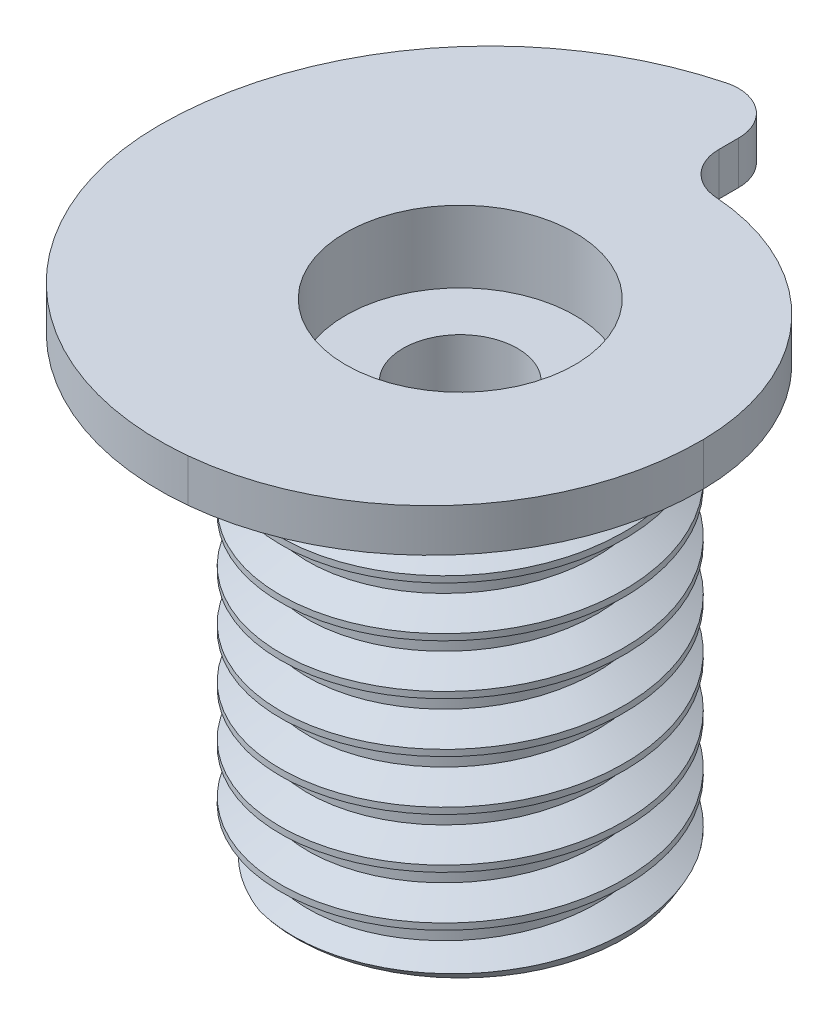
SolidWorks part; units mm, degrees
ref_plane "Front Plane" through (0, 0, 0) normal (0, 0, 1) x (1, 0, 0)
ref_plane "Top Plane" through (0, 0, 0) normal (0, 1, 0) x (1, 0, 0)
ref_plane "Right Plane" through (0, 0, 0) normal (1, 0, 0) x (0, 0, -1)
sketch "Sketch1" plane through (0, 0, 0) normal (1, 0, 0) x (0, 0, -1)
  line L4 (12, 30) -> (12, 0)
  line L6 (0, 0) -> (0, 30) construction
  line L7 (12, 30) -> (4, 30)
  line L10 (4, 30) -> (4, 5)
  line L11 (4, 5) -> (8, 5)
  line L12 (8, 5) -> (8, 0)
  line L13 (8, 0) -> (12, 0)
  dimension "D1" = 8
  dimension "D2" = 8
  dimension "D3" = 5
  dimension "D6" = 30
  dimension "D7" = 12
revolve "Revolve1" add sketch "Sketch1" angle 360 about L6
chamfer "Chamfer1" distance 1 angle 30 1 edges at (0, 0, -12) first distance on face at (0, 30, -12)
thread "Thread1" pitch 3.5 method cut profile "Thread Profile1" start angle 0, offset 0, length 48, pitch 3.5, diameter 24
ref_plane "Plane1" through (-12, 30, 0) normal (0, 0, 1) x (-1, 0, 0)
sketch "Thread Profile1" plane through (-12, 30, 0) normal (0, 0, 1) x (-1, 0, 0)
  line L0 (0, 0) -> (0, 3.5) construction
  line L11 (0, 0) -> (0, 3.0625)
  line L12 (0, 3.0625) -> (-1.8944, 1.9687)
  line L13 (-1.8944, 1.9687) -> (-1.8944, 1.0937)
  line L15 (-1.8944, 1.0937) -> (0, 0)
  line L17 (-1.8944, 1.5312) -> (0, 1.5312) construction
  point P2 (0, 0)
  dimension "Pitch" = 3.5
  dimension "Profile_Angle" = 60
  dimension "Profile_Land" = 0.875
  dimension "Profile_Height" = 1.8944
sketch "Sketch2" plane through (0, 30, 0) normal (0, 1, 0) x (1, 0, 0)
  line L1 (0, 11.547) -> (-10, -5.7735) construction
  line L2 (-10, -5.7735) -> (10, -5.7735) construction
  line L3 (10, -5.7735) -> (0, 11.547) construction
  circle A0 centre (0, 0) radius 5.7735 construction
  circle A1 centre (0, 11.547) radius 1.5
  circle A2 centre (10, -5.7735) radius 1.5
  circle A3 centre (-10, -5.7735) radius 1.5
  dimension "D2" = 3
  dimension "D1" = 20
extrude "Cut-Extrude1" [suppressed] cut sketch "Sketch2" against normal blind 4
sketch "Sketch3" plane through (0, 30, 0) normal (0, 1, 0) x (1, 0, 0)
  line L0 (0, 23) -> (0, -23) construction
  line L1 (-23, 0) -> (23, 0) construction
  line L2 (0, 23) -> (0, 15)
  circle A1 centre (0, 0) radius 15 construction
  circle A2 centre (0, 0) radius 17 construction
  circle A3 centre (0, 0) radius 19 construction
  circle A4 centre (0, 0) radius 21 construction
  circle A5 centre (0, 0) radius 23 construction
  arc A6 (0, 23) -> (-21, 0) centre (2.0952, 0) ccw
  arc A7 (-21, 0) -> (0, -19) centre (-1.9048, 0) ccw
  arc A8 (0, -19) -> (17, 0) centre (-1.8838, -0.2092) ccw
  arc A9 (17, 0) -> (0, 15) centre (1.7331, -0.1692) ccw
  dimension "D1" = 30
  dimension "D2" = 2
  dimension "D3" = 2
  dimension "D4" = 2
  dimension "D5" = 2
extrude "Boss-Extrude1" add sketch "Sketch3" along normal blind 3
sketch "Sketch4" plane through (0, 33, 0) normal (0, 1, 0) x (1, 0, 0)
  circle A2 centre (0, 0) radius 8
  dimension "D1" = 16
extrude "Cut-Extrude2" cut sketch "Sketch4" against normal blind 5
fillet "Fillet1" radius 3 2 edges at (0, 31.5, -15) (0, 31.5, -23)
sketch "Sketch5" plane through (0, 33, 0) normal (0, 1, 0) x (1, 0, 0)
  arc A0 (-6.606, 16.744) -> (-18, 0) centre (0, 0) ccw construction
  arc A1 (-7.5235, 19.0695) -> (-20.5, 0) centre (0, 0) ccw
  arc A2 (-5.6885, 14.4184) -> (-15.5, 0) centre (0, 0) ccw
  arc A3 (-5.6885, 14.4184) -> (-7.5235, 19.0695) centre (-6.606, 16.744) ccw
  arc A4 (-20.5, 0) -> (-15.5, 0) centre (-18, 0) ccw
  arc A5 (-8.6169, -12.278) -> (8.6169, -12.278) centre (0, 0) ccw construction
  arc A6 (-9.7658, -13.9151) -> (9.7658, -13.9151) centre (0, 0) ccw
  arc A7 (-7.4679, -10.6409) -> (7.4679, -10.6409) centre (0, 0) ccw
  arc A8 (-7.4679, -10.6409) -> (-9.7658, -13.9151) centre (-8.6169, -12.278) ccw
  arc A9 (9.7658, -13.9151) -> (7.4679, -10.6409) centre (8.6169, -12.278) ccw
  arc A10 (13.9041, 1.6355) -> (6.0016, 12.6484) centre (0, 0) ccw construction
  arc A11 (15.3939, 1.8107) -> (6.6446, 14.0035) centre (0, 0) ccw
  arc A12 (12.4144, 1.4603) -> (5.3586, 11.2932) centre (0, 0) ccw
  arc A13 (12.4144, 1.4603) -> (15.3939, 1.8107) centre (13.9041, 1.6355) ccw
  arc A14 (6.6446, 14.0035) -> (5.3586, 11.2932) centre (6.0016, 12.6484) ccw
  point P4 (-14.8813, 10.1265)
  point P9 (0, -15)
  point P18 (11.3745, 8.1621)
  dimension "D1" = 18
  dimension "D2" = 2.5
  dimension "D3" = 15
  dimension "D4" = 2
  dimension "D5" = 14
  dimension "D6" = 1.5
